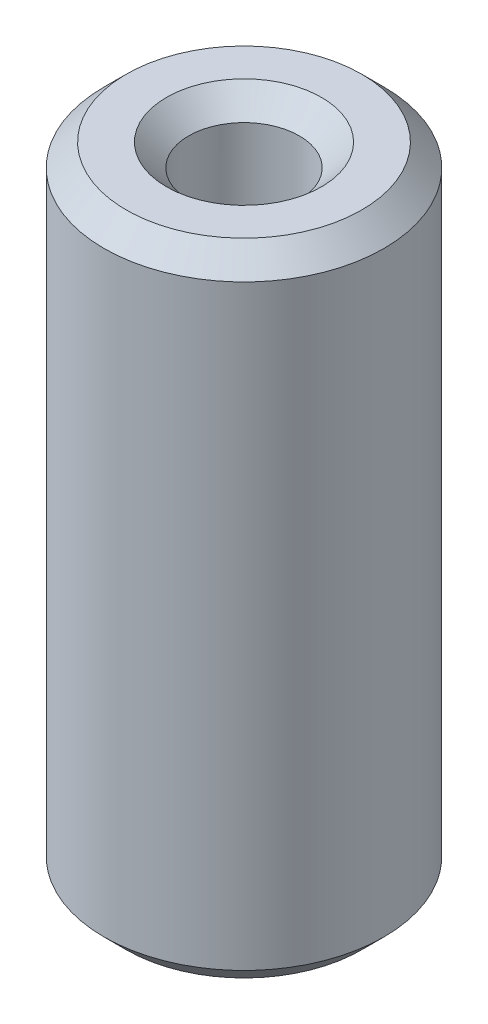
SolidWorks part; units mm, degrees
ref_plane "Front Plane" through (0, 0, 0) normal (0, 0, 1) x (1, 0, 0)
ref_plane "Top Plane" through (0, 0, 0) normal (0, 1, 0) x (1, 0, 0)
ref_plane "Right Plane" through (0, 0, 0) normal (1, 0, 0) x (0, 0, -1)
sketch "Sketch1" plane through (0, 0, 0) normal (0, 1, 0) x (1, 0, 0)
  circle A0 centre (0, 0) radius 10
  dimension "SLEEVE_OD" = 20
extrude "Boss-Extrude1" add sketch "Sketch1" along normal blind 45.7951
sketch "Sketch2" plane through (0, 0, 0) normal (0, 1, 0) x (1, 0, 0)
  circle A0 centre (0, 0) radius 3.9524
  dimension "BORE_D" = 7.9047
extrude "Cut-Extrude1" cut sketch "Sketch2" along normal through all
chamfer "Chamfer1" distance 1.5879 angle 45 4 edges at (0, 45.7951, 3.9524) (0, 0, 3.9524) (0, 0, 10) (0, 45.7951, 10)
